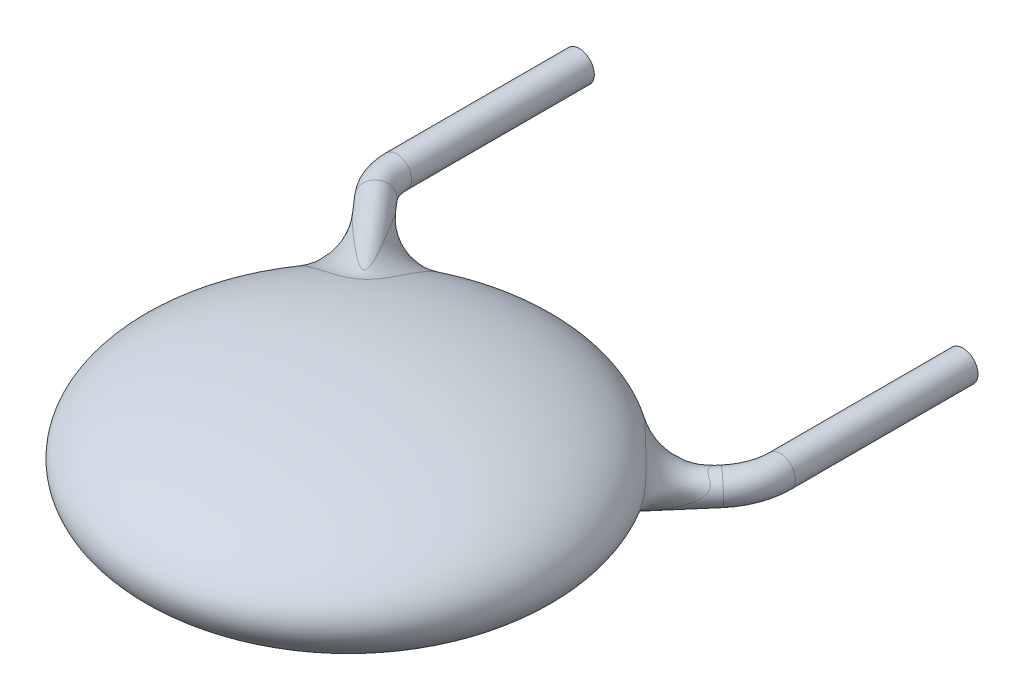
SolidWorks part; units mm, degrees
ref_plane "Front Plane" through (0, 0, 0) normal (0, 0, 1) x (1, 0, 0)
ref_plane "Top Plane" through (0, 0, 0) normal (0, 1, 0) x (1, 0, 0)
ref_plane "Right Plane" through (0, 0, 0) normal (1, 0, 0) x (0, 0, -1)
sketch "Sketch3" plane through (0, 0, 0) normal (1, 0, 0) x (0, 0, -1)
  line L1 (-6.25, 1.5) -> (-6.25, 0.5)
  line L2 (-6.25, 0.5) -> (-5.9686, 0.5)
  line L4 (-5.9686, 0.5) -> (-5.9686, -0.5)
  line L5 (-6.25, -0.5) -> (-5.9686, -0.5)
  line L6 (-6.25, -0.5) -> (-6.25, -1.5)
  ellipse E0 centre (-6.25, 0) end of major axis (-2, 0) minor radius 1.5 (-6.25, 1.5) -> (-6.25, -1.5) cw
  point P1 (0, 0)
  point P10 (0, 0)
  point P11 (-6.25, 0)
  point P14 (0, 0)
  dimension "D1" = 8.5
  dimension "D2" = 3
  dimension "D3" = 2
  dimension "D4" = 1
revolve "Revolve1" add sketch "Sketch3" angle 360 about L1
sketch "Sketch149" plane through (0, 0, 0) normal (0, 0, 1) x (1, 0, 0)
  line L0 (-3.6637, 0.8) -> (3.6637, -0.8) construction
  line L2 (-0.2814, 0.5) -> (0.2814, 0.5) construction
  line L3 (-3.6637, 0.5) -> (3.6637, -0.5) construction
  circle A0 centre (-3.6637, 0.8) radius 0.3
  point P2 (0, 0)
  point P9 (0, 0)
  point P10 (0, 0)
  point P11 (3.6637, -0.5)
  point P12 (0, 0)
  point P15 (0, 0)
  point P16 (0, 0)
  dimension "D3" = 0.6
  dimension "D1" = 7.5
sketch3d "3DSketch4"
  line L0 (-3.6637, 0.5, -2) -> (-3.6637, 0.5, 1.6285)
  line L1 (-3.4211, 0.5, 2.2814) -> (0, 0.5, 6.25)
  line L2 (0, 1.5, 6.25) -> (0, 0.5, 6.25) construction
  line L3 (3.6637, -0.5, -2) -> (3.6637, -0.5, 1.6285)
  line L4 (3.4211, -0.5, 2.2814) -> (0, -0.5, 6.25)
  line L6 (0, -0.5, 6.25) -> (0, 0.5, 6.25)
  line L7 (3.6637, -0.5, 2) -> (-3.6637, 0.5, 2) construction
  line L8 (3.6637, -0.5, -2) -> (-3.6637, 0.5, -2) construction
  line L11 (-3.6637, 0.5, 0) -> (3.6637, -0.5, 0) construction
  arc A6 (-3.6637, 0.5, 1.6285) -> (-3.4211, 0.5, 2.2814) centre (-2.6637, 0.5, 1.6285) ccw
  arc A7 (3.6637, -0.5, 1.6285) -> (3.4211, -0.5, 2.2814) centre (2.6637, -0.5, 1.6285) ccw
  point P8 (-3.6637, 0.5, 2)
  point P10 (-2.6637, 1.5, 1.6285)
  point P13 (3.6637, -0.5, 2)
  point P15 (2.6637, -1.5, 1.6285)
  point P17 (0, 0, 6.25)
  dimension "D2" = 1
  dimension "D1" = 2
sweep "Sweep1" add profiles "Sketch149" path "3DSketch4"
fillet "Fillet1" radius 1 2 edges at (2.6444, -0.4643, 3.194) (-2.1923, 0.7328, 3.2591)
